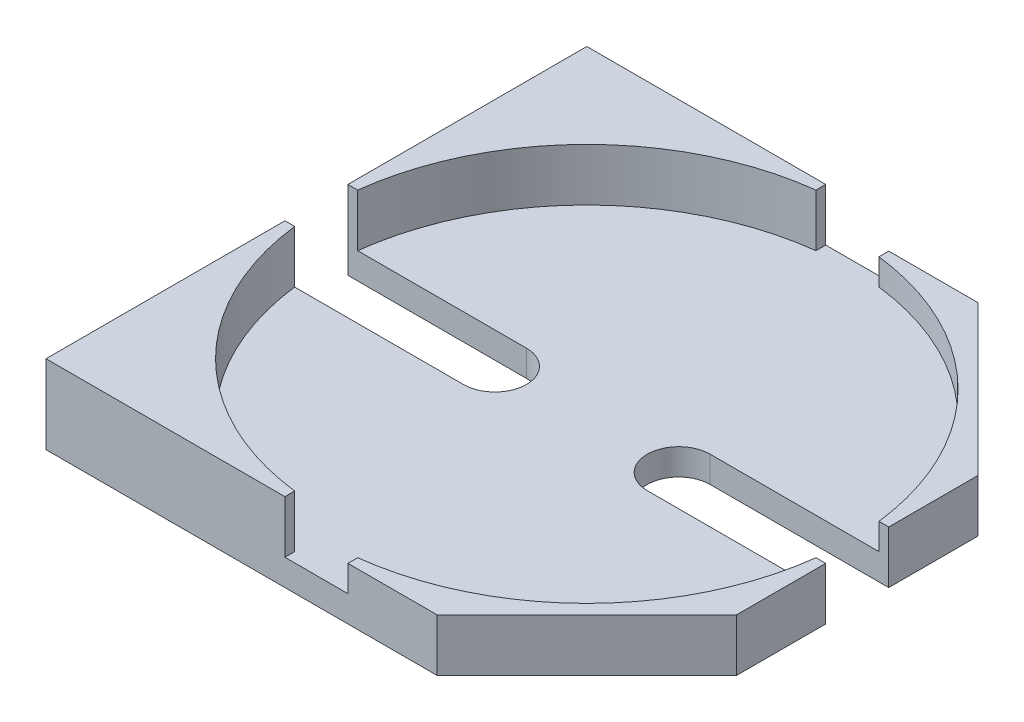
SolidWorks part; units mm, degrees
ref_plane "Front Plane" through (0, 0, 0) normal (0, 0, 1) x (1, 0, 0)
ref_plane "Top Plane" through (0, 0, 0) normal (0, 1, 0) x (1, 0, 0)
ref_plane "Right Plane" through (0, 0, 0) normal (1, 0, 0) x (0, 0, -1)
sketch "Sketch1" plane through (0, 0, 0) normal (0, 1, 0) x (1, 0, 0)
  line L0 (2.3, 5.15) -> (5.15, 2.3)
  line L1 (2.3, 5.15) -> (-5.15, 5.15)
  line L2 (5.15, 2.3) -> (5.15, 0.6)
  line L3 (2.3, -5.15) -> (-5.15, -5.15)
  line L4 (-5.15, 5.15) -> (-5.15, 0.6)
  line L5 (77.9244, 77.9244) -> (-5.15, -5.15) construction
  line L6 (43.6295, -43.6295) -> (-5.15, 5.15) construction
  line L7 (2.3, -5.15) -> (5.15, -2.3)
  line L8 (-1.75, 0) -> (1.75, 0) construction
  line L9 (-1.75, 0.6) -> (-5.15, 0.6)
  line L10 (-1.75, -0.6) -> (-5.15, -0.6)
  line L11 (1.75, 0.6) -> (5.15, 0.6)
  line L12 (1.75, -0.6) -> (5.15, -0.6)
  line L13 (-5.15, -0.6) -> (-5.15, -5.15)
  line L14 (5.15, -0.6) -> (5.15, -2.3)
  arc A0 (-1.75, -0.6) -> (-1.75, 0.6) centre (-1.75, 0) ccw
  arc A1 (1.75, 0.6) -> (1.75, -0.6) centre (1.75, 0) ccw
  point P0 (0, 0)
  point P14 (0, 0)
  dimension "D3" = 10.3
  dimension "D1" = 45
  dimension "D2" = 45
  dimension "A" = 10.3
  dimension "W" = 1.2
  dimension "T" = 1.7
  dimension "B" = 10.3
  dimension "P" = 2.3
extrude "Base" add sketch "Sketch1" along normal blind 0.5
sketch "Sketch2" plane through (0, 0.5, 0) normal (0, 1, 0) x (1, 0, 0)
  line L0 (-0.6, 5.15) -> (-0.6, 4.9639)
  line L1 (0.6, 5.15) -> (0.6, 4.9639)
  line L2 (-0.6, -5.15) -> (-0.6, -4.9639)
  line L3 (0.6, -5.15) -> (0.6, -4.9639)
  line L4 (0.6, -5.15) -> (2.3, -5.15)
  line L5 (-0.6, 5.15) -> (-5.15, 5.15)
  line L12 (-5.15, -0.6) -> (-5.15, -5.15)
  line L13 (-5.15, -5.15) -> (2.3, -5.15)
  line L14 (2.3, -5.15) -> (5.15, -2.3)
  line L15 (5.15, -2.3) -> (5.15, -0.6)
  line L16 (5.15, -0.6) -> (1.75, -0.6)
  line L17 (1.75, 0.6) -> (5.15, 0.6)
  line L18 (5.15, 0.6) -> (5.15, 2.3)
  line L19 (5.15, 2.3) -> (2.3, 5.15)
  line L20 (2.3, 5.15) -> (-5.15, 5.15)
  line L21 (-5.15, 5.15) -> (-5.15, 0.6)
  line L22 (-5.15, 0.6) -> (-1.75, 0.6)
  line L23 (-1.75, -0.6) -> (-5.15, -0.6)
  line L24 (-5.15, -0.6) -> (-5.15, -5.15)
  line L25 (-5.15, -5.15) -> (-0.6, -5.15)
  line L26 (2.3, -5.15) -> (5.15, -2.3)
  line L27 (5.15, -2.3) -> (5.15, -0.6)
  line L28 (5.15, -0.6) -> (4.9639, -0.6)
  line L29 (4.9639, 0.6) -> (5.15, 0.6)
  line L30 (5.15, 0.6) -> (5.15, 2.3)
  line L31 (5.15, 2.3) -> (2.3, 5.15)
  line L32 (2.3, 5.15) -> (0.6, 5.15)
  line L33 (-5.15, 5.15) -> (-5.15, 0.6)
  line L34 (-5.15, 0.6) -> (-4.9639, 0.6)
  line L35 (-4.9639, -0.6) -> (-5.15, -0.6)
  arc A0 (-4.9639, -0.6) -> (-0.6, -4.9639) centre (0, 0) ccw
  arc A1 (4.9639, 0.6) -> (0.6, 4.9639) centre (0, 0) ccw
  arc A2 (0.6, -4.9639) -> (4.9639, -0.6) centre (0, 0) ccw
  arc A3 (1.75, 0.6) -> (1.75, -0.6) centre (1.75, 0) ccw
  arc A4 (-1.75, -0.6) -> (-1.75, 0.6) centre (-1.75, 0) ccw
  arc A7 (-0.6, 4.9639) -> (-4.9639, 0.6) centre (0, 0) ccw
  line M1 (-5.15, -0.6) -> (-5.15, -5.15)
  line M2 (-5.15, -5.15) -> (2.3, -5.15)
  line M3 (2.3, -5.15) -> (5.15, -2.3)
  line M4 (5.15, -2.3) -> (5.15, -0.6)
  line M5 (5.15, -0.6) -> (1.75, -0.6)
  line M7 (1.75, 0.6) -> (5.15, 0.6)
  line M8 (5.15, 0.6) -> (5.15, 2.3)
  line M9 (5.15, 2.3) -> (2.3, 5.15)
  line M10 (2.3, 5.15) -> (-5.15, 5.15)
  line M11 (-5.15, 5.15) -> (-5.15, 0.6)
  line M12 (-5.15, 0.6) -> (-1.75, 0.6)
  line M14 (-1.75, -0.6) -> (-5.15, -0.6)
  dimension "D1" = 0
  dimension "D" = 10
extrude "Back Height" add sketch "Sketch2" along normal blind 1 contours A7 L0 M10 M11 M12 | A0 L2 M14 M1 M2 region at (-3.9004, 0.5, -3.9004) region at (-3.9004, 0.5, 3.9004)
extrude "Front Height" add sketch "Sketch2<3>" along normal blind 0.5 contours A1 L1 M7 M8 M9 M10 | A2 L3 M2 M3 M4 M5 region at (1.45, 0.5, -5.0857) region at (5.0569, 0.5, 0.6643)
sketch "Sketch2<3>" plane through (0, 0.5, 0) normal (0, 1, 0) x (1, 0, 0) same geometry as "Sketch2"
